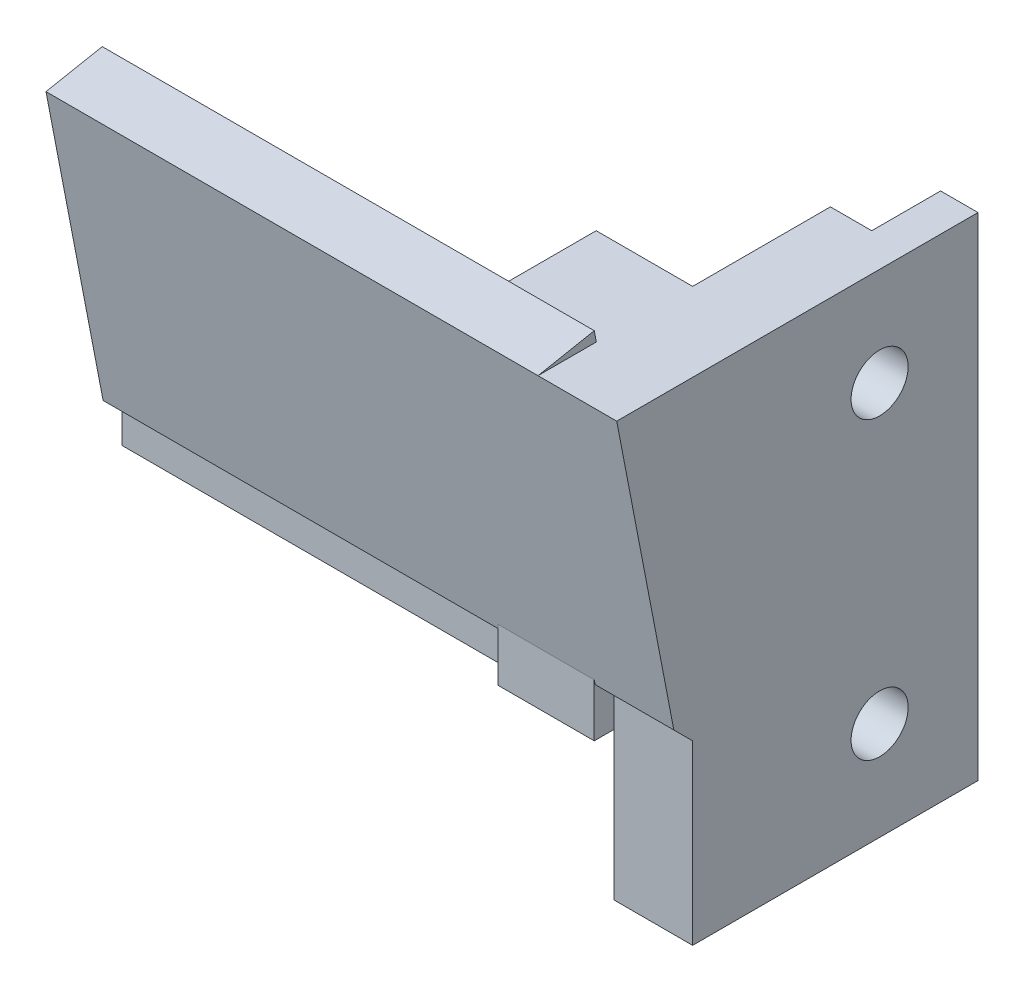
SolidWorks part; units mm, degrees
ref_plane "前视基准面" through (0, 0, 0) normal (0, 0, 1) x (1, 0, 0)
ref_plane "上视基准面" through (0, 0, 0) normal (0, 1, 0) x (1, 0, 0)
ref_plane "右视基准面" through (0, 0, 0) normal (1, 0, 0) x (0, 0, -1)
other "Configuration Table"
sketch "草图1" plane through (0, 0, 0) normal (1, 0, 0) x (0, 0, -1)
  line L0 (0, 0) -> (-10, 0)
  line L1 (-10, 0) -> (-17.7164, 40)
  line L2 (-17.7164, 40) -> (-12, 41.1027)
  line L3 (-12, 41.1027) -> (-6, 10)
  line L4 (-6, 10) -> (0, 10)
  line L5 (0, 10) -> (0, 0)
  dimension "D1" = 10
  dimension "D2" = 6
  dimension "D3" = 10
  dimension "D4" = 6
  dimension "D5" = 40
extrude "凸台-拉伸1" add sketch "草图1" along normal blind 50
sketch "草图2" plane through (0, 0, 0) normal (0, -1, 0) x (1, 0, 0)
  line L4 (0, 10) -> (0, 0)
  line L5 (0, 0) -> (50, 0)
  line L6 (50, 0) -> (50, 10)
  line L7 (50, 10) -> (0, 10)
  line L8 (0, 10) -> (0, 0)
  line L9 (0, 0) -> (50, 0)
  line L10 (50, 0) -> (50, 10)
  line L11 (50, 10) -> (0, 10)
  dimension "D1" = 0
extrude "凸台-拉伸2" add sketch "草图2" along normal blind 10
sketch "草图3" plane through (0, 0, 0) normal (-1, 0, 0) x (0, 0, 1)
  line L1 (0, 10) -> (10, 10)
  line L2 (0, 10) -> (0, -10)
  line L3 (0, -10) -> (10, -10)
  line L4 (10, 10) -> (10, -10)
extrude "凸台-拉伸3" add sketch "草图3" along normal blind 20
sketch "草图4" plane through (0, 10, 0) normal (0, 1, 0) x (1, 0, 0)
  line L1 (-20, 0) -> (0, 0)
  line L2 (-20, 0) -> (-20, -10)
  line L3 (-20, -10) -> (0, -10)
  line L4 (0, 0) -> (0, -10)
extrude "凸台-拉伸4" add sketch "草图4" along normal blind 30
sketch "草图5" plane through (50, 0, 0) normal (1, 0, 0) x (0, 0, -1)
  line L0 (-10, 10) -> (-11.9291, 10)
  line L1 (-17.7164, 40) -> (-10, 0) construction
  line L2 (-11.9291, 10) -> (-10, 0)
  line L3 (-10, 0) -> (-10, 10)
extrude "切除-拉伸1" cut sketch "草图5" against normal up to surface (50 mm away) up to face at (0, 27.9595, 12.4291)
chamfer "倒角1" distance 2 angle 45 1 edges at (25, 10, 10)
sketch "草图9" plane through (0, 0, 10) normal (0, 0, 1) x (1, 0, 0)
  line L0 (-20, 40) -> (-10, 40) construction
  line L1 (-20, 40) -> (0, 40) construction
  line L2 (-10, 40) -> (-10, 30) construction
  line L3 (50, -10) -> (50, 0) construction
  line L4 (50, -10) -> (50, 8) construction
  line L5 (50, 0) -> (-10, 0) construction
  line L6 (-20, -10) -> (-20, 40) construction
  circle A0 centre (-10, 30) radius 1.5
  circle A1 centre (-10, 0) radius 1.5
  dimension "D3" = 3
  dimension "D5" = 3
  dimension "D4" = 10
  dimension "D1" = 10
  dimension "D2" = 10
extrude "切除-拉伸2" cut sketch "草图9" against normal through all
sketch "草图12" plane through (0, 0, 10) normal (0, 0, 1) x (1, 0, 0)
  line L6 (0, 30.7352) -> (0, 40)
  line L7 (0, 30.7352) -> (0, 40)
  line L8 (0, 40) -> (-20, 40)
  line L9 (50, -10) -> (50, 8)
  line L10 (50, 8) -> (0, 8)
  line L11 (0, 8) -> (0, 30.7352)
  line L15 (50, -10) -> (50, 8)
  line L16 (50, 8) -> (0, 8)
  line L17 (0, 8) -> (0, 30.7352)
  line L19 (0, 40) -> (-20, 40)
  line L20 (-20, 40) -> (-20, -10)
  line L21 (-20, 40) -> (-20, -10)
  line L22 (-20, -10) -> (50, -10)
  line L23 (-20, -10) -> (50, -10)
  dimension "D1" = 0
extrude "切除-拉伸4" cut sketch "草图12" against normal blind 6
sketch "草图13" plane through (0, 8, 0) normal (0, -1, 0) x (1, 0, 0)
  line L0 (50, 4) -> (0, 4) construction
  line L1 (0, 10) -> (4, 10)
  line L2 (0, 10) -> (0, 4)
  line L3 (0, 4) -> (4, 4)
  line L4 (4, 10) -> (4, 4)
  line L6 (50, 10) -> (46, 10)
  line L7 (50, 10) -> (50, 4)
  line L8 (50, 4) -> (46, 4)
  line L9 (46, 10) -> (46, 4)
  dimension "D1" = 4
  dimension "D2" = 4
extrude "凸台-拉伸12" add sketch "草图13" along normal up to surface (18 mm away) up to face at (15, -10, 2)
sketch "草图15" plane through (0, 0, 0) normal (0, 0, -1) x (-1, 0, 0)
  line L0 (-25, 10) -> (-25, 20.01) construction
  line L1 (0, 40) -> (20, 40) construction
  line L2 (0, 40) -> (0, -10) construction
  line L3 (0, -10) -> (20, -10) construction
  line L4 (20, 40) -> (20, -10) construction
  line L5 (-50, 10) -> (0, 10) construction
  line L6 (-50, -10) -> (-70, -10)
  line L7 (-70, 40) -> (-70, -10)
  line L8 (-50, 40) -> (-70, 40)
  line L9 (-50, 40) -> (-50, -10)
  circle A0 centre (10, 30) radius 1.5 construction
  circle A1 centre (-60, 30) radius 1.5
extrude "凸台-拉伸14" add sketch "草图15" against normal up to surface (4 mm away) up to face at (-8.5, 30, 4)
sketch "草图16" plane through (0, 0, 4) normal (0, 0, 1) x (1, 0, 0)
  line L5 (-20, -10) -> (0, -10)
  line L6 (0, -10) -> (0, 10)
  line L7 (0, 10) -> (0, 40)
  line L8 (0, 40) -> (-20, 40)
  line L9 (-20, 40) -> (-20, -10)
  line L10 (-20, -10) -> (0, -10)
  line L11 (0, -10) -> (0, 10)
  line L12 (0, 10) -> (0, 40)
  line L13 (0, 40) -> (-20, 40)
  line L14 (-20, 40) -> (-20, -10)
  dimension "D1" = 0
extrude "切除-拉伸5" cut sketch "草图16" against normal up to surface (4 mm away) up to face at (-8.5, 30, 0)
sketch "草图17" plane through (0, 0, 4) normal (0, 0, 1) x (1, 0, 0)
  line L1 (50, 10) -> (70, 10)
  line L2 (50, 10) -> (50, -10)
  line L3 (50, -10) -> (70, -10)
  line L4 (70, 10) -> (70, -10)
extrude "凸台-拉伸15" add sketch "草图17" along normal up to surface (6 mm away) up to face at (48, -1, 10)
sketch "草图18" plane through (0, 10, 0) normal (0, 1, 0) x (1, 0, 0)
  line L1 (0, 0) -> (50, 0)
  line L2 (0, 0) -> (0, -6)
  line L3 (0, -6) -> (50, -6)
  line L4 (50, 0) -> (50, -6)
extrude "切除-拉伸6" cut sketch "草图18" against normal up to surface (20 mm away) up to face at (30, -10, 6)
sketch "草图19" plane through (0, -10, 0) normal (0, -1, 0) x (1, 0, 0)
  line L1 (50, 6) -> (46, 6)
  line L2 (50, 6) -> (50, 10)
  line L3 (50, 10) -> (46, 10)
  line L4 (46, 6) -> (46, 10)
  line L5 (4, 6) -> (0, 6)
  line L6 (4, 6) -> (4, 10)
  line L7 (4, 10) -> (0, 10)
  line L8 (0, 6) -> (0, 10)
extrude "切除-拉伸9" cut sketch "草图19" against normal up to surface (18 mm away) up to face at (25, 8, 8)
sketch "草图20" plane through (0, 0, 4) normal (0, 0, 1) x (1, 0, 0)
  line L0 (50, 10) -> (70, 10) construction
  line L1 (50, 40) -> (55, 40)
  line L2 (50, 40) -> (50, 10)
  line L3 (50, 10) -> (55, 10)
  line L4 (55, 40) -> (55, 10)
  dimension "D1" = 5
extrude "凸台-拉伸16" add sketch "草图20" along normal up to surface (13.7164 mm away) up to face at (25, 24.9561, 14.8143)
sketch "草图21" plane through (0, 8, 0) normal (0, -1, 0) x (1, 0, 0)
  line L4 (50, 10) -> (0, 10)
  line L5 (0, 10) -> (0, 6)
  line L6 (0, 6) -> (50, 6)
  line L8 (50, 10) -> (0, 10)
  line L10 (0, 6) -> (50, 6)
  line L12 (0, 10) -> (0, 6)
  line L14 (50, 6) -> (50, 10)
  line L15 (50, 6) -> (50, 10)
  dimension "D1" = 0
extrude "凸台-拉伸17" add sketch "草图21" along normal up to surface (18 mm away) up to face at (60, -10, 5)
sketch "草图22" plane through (0, 0, 10) normal (0, 0, 1) x (1, 0, 0)
  line L0 (70, 10) -> (70, -10) construction
  line L1 (10, 5) -> (70, 5)
  line L2 (10, 5) -> (10, -5)
  line L3 (10, -5) -> (70, -5)
  line L4 (70, 5) -> (70, -5)
  line L5 (55, 10) -> (70, 10) construction
  line L6 (70, -10) -> (0, -10) construction
  line L8 (0, -10) -> (0, 8) construction
  dimension "D1" = 5
  dimension "D2" = 5
  dimension "D3" = 10
extrude "切除-拉伸10" cut sketch "草图22" against normal up to surface (6 mm away) up to face at (61.5, 30, 4)
sketch "草图23" plane through (0, 0, 0) normal (0, 0, -1) x (-1, 0, 0)
  line L0 (-60, 30) -> (-60, 0) construction
  circle A0 centre (-60, 0) radius 1.5
  dimension "D1" = 3
extrude "切除-拉伸11" cut sketch "草图23" against normal up to surface (4 mm away) up to face at (60, 0, 4)
chamfer "倒角2" distance 2 angle 45 1 edges at (52.5, 10, 10)
sketch "草图24" plane through (0, 0, 4) normal (0, 0, 1) x (1, 0, 0)
  circle A0 centre (60, 30) radius 3
  circle A1 centre (60, 0) radius 3
  dimension "D1" = 6
  dimension "D2" = 6
extrude "切除-拉伸12" cut sketch "草图24" against normal blind 2
sketch "草图25" plane through (0, 0, 10) normal (0, 0, 1) x (1, 0, 0)
  line L1 (55, 40) -> (70, 40)
  line L2 (55, 40) -> (55, -10)
  line L3 (55, -10) -> (70, -10)
  line L4 (70, 40) -> (70, -10)
extrude "切除-拉伸13" cut sketch "草图25" against normal up to surface (10 mm away) up to face at (58.5, 0, 0)
sketch "草图26" plane through (0, 0, 0) normal (0, 0, -1) x (-1, 0, 0)
  line L4 (-50, 40) -> (-55, 40)
  line L5 (-55, 40) -> (-55, -10)
  line L6 (-55, -10) -> (-50, -10)
  line L7 (-50, -10) -> (-50, 40)
  line L8 (-50, 40) -> (-55, 40)
  line L9 (-55, 40) -> (-55, -10)
  line L10 (-55, -10) -> (-50, -10)
  line L11 (-50, -10) -> (-50, 40)
  dimension "D1" = 0
extrude "凸台-拉伸18" add sketch "草图26" along normal blind 19
sketch "草图27" plane through (50, 0, 0) normal (-1, 0, 0) x (0, 0, 1)
  line L0 (6, -10) -> (-19, -10) construction
  line L1 (-19, 40) -> (-12, 40)
  line L2 (-19, 40) -> (-19, -10)
  line L3 (-19, -10) -> (-12, -10)
  line L4 (-12, 40) -> (-12, -10)
  dimension "D1" = 7
extrude "切除-拉伸14" cut sketch "草图27" against normal blind 4.2
sketch "草图28" plane through (55, 0, 0) normal (1, 0, 0) x (0, 0, -1)
  line L10 (-10, -10) -> (19, -10)
  line L11 (19, -10) -> (19, 40)
  line L12 (19, 40) -> (-17.7164, 40)
  line L13 (-17.7164, 40) -> (-11.9121, 9.9121)
  line L14 (-11.9121, 9.9121) -> (-10, 8)
  line L15 (-10, 8) -> (-10, 5)
  line L16 (-10, 5) -> (-4, 5)
  line L17 (-4, 5) -> (-4, -5)
  line L18 (-4, -5) -> (-10, -5)
  line L19 (-10, -5) -> (-10, -10)
  line L20 (-10, -10) -> (19, -10)
  line L21 (19, -10) -> (19, 40)
  line L22 (19, 40) -> (-17.7164, 40)
  line L23 (-17.7164, 40) -> (-11.9121, 9.9121)
  line L24 (-11.9121, 9.9121) -> (-10, 8)
  line L25 (-10, 8) -> (-10, 5)
  line L26 (-10, 5) -> (-4, 5)
  line L27 (-4, 5) -> (-4, -5)
  line L28 (-4, -5) -> (-10, -5)
  line L29 (-10, -5) -> (-10, -10)
  dimension "D1" = 0
extrude "凸台-拉伸19" add sketch "草图28" along normal blind 3
sketch "草图29" plane through (58, 0, 0) normal (1, 0, 0) x (0, 0, -1)
  line L0 (19, 40) -> (9, 40) construction
  line L1 (19, 40) -> (-17.7164, 40) construction
  line L2 (9, 40) -> (9, 30) construction
  line L3 (9, 30) -> (9, 0) construction
  circle A0 centre (9, 30) radius 1.5
  circle A1 centre (9, 0) radius 1.5
  dimension "D4" = 3
  dimension "D5" = 3
  dimension "D1" = 10
  dimension "D2" = 10
  dimension "D3" = 30
extrude "切除-拉伸15" cut sketch "草图29" against normal blind 13
sketch "草图30" plane through (58, 0, 0) normal (1, 0, 0) x (0, 0, -1)
  circle A0 centre (9, 30) radius 2.9
  circle A1 centre (9, 0) radius 2.9
  dimension "D1" = 5.8
  dimension "D2" = 5.8
extrude "切除-拉伸16" cut sketch "草图30" against normal offset from surface (6 mm away) 2 up to face at (50, 30, -7.5)
sketch "草图31" plane through (10, 0, 0) normal (1, 0, 0) x (0, 0, -1)
  line L4 (-6, 5) -> (-10, 5)
  line L5 (-10, 5) -> (-10, -5)
  line L6 (-10, -5) -> (-6, -5)
  line L7 (-6, -5) -> (-6, 5)
  line L8 (-6, 5) -> (-10, 5)
  line L9 (-10, 5) -> (-10, -5)
  line L10 (-10, -5) -> (-6, -5)
  line L11 (-6, -5) -> (-6, 5)
  dimension "D1" = 0
extrude "切除-拉伸17" cut sketch "草图31" against normal up to surface (10 mm away) up to face at (0, 12.7164, 10.5184)
sketch "草图32" plane through (0, 0, 4) normal (0, 0, 1) x (1, 0, 0)
  line L4 (50, -5) -> (58, -5)
  line L5 (58, -5) -> (58, 5)
  line L6 (58, 5) -> (50, 5)
  line L7 (50, 5) -> (50, -5)
  line L8 (50, -5) -> (58, -5)
  line L9 (58, -5) -> (58, 5)
  line L10 (58, 5) -> (50, 5)
  line L11 (50, 5) -> (50, -5)
  dimension "D1" = 0
extrude "凸台-拉伸20" add sketch "草图32" along normal up to surface (6 mm away) up to face at (29, -7.5, 10)
sketch "草图33" plane through (0, 0, 10) normal (0, 0, 1) x (1, 0, 0)
  line L1 (50, -5) -> (0, -5)
  line L2 (50, -5) -> (50, -10)
  line L3 (50, -10) -> (0, -10)
  line L4 (0, -5) -> (0, -10)
extrude "切除-拉伸18" cut sketch "草图33" against normal up to surface (4 mm away) up to face at (25, 7.5, 6)
sketch "草图34" plane through (0, 40, 0) normal (0, 1, 0) x (1, 0, 0)
  line L0 (50, -11.7873) -> (50, 12) construction
  line L1 (50, -2) -> (40.2, -2)
  line L2 (50, -2) -> (50, -12)
  line L3 (50, -12) -> (40.2, -12)
  line L4 (40.2, -2) -> (40.2, -12)
  line L6 (54.2, 19) -> (58, 19) construction
  line L11 (50, -12) -> (0, -12) construction
  dimension "D1" = 21
  dimension "D2" = 9.8
extrude "凸台-拉伸21" add sketch "草图34" against normal up to surface (35 mm away) up to face at (25, 5, 8)
